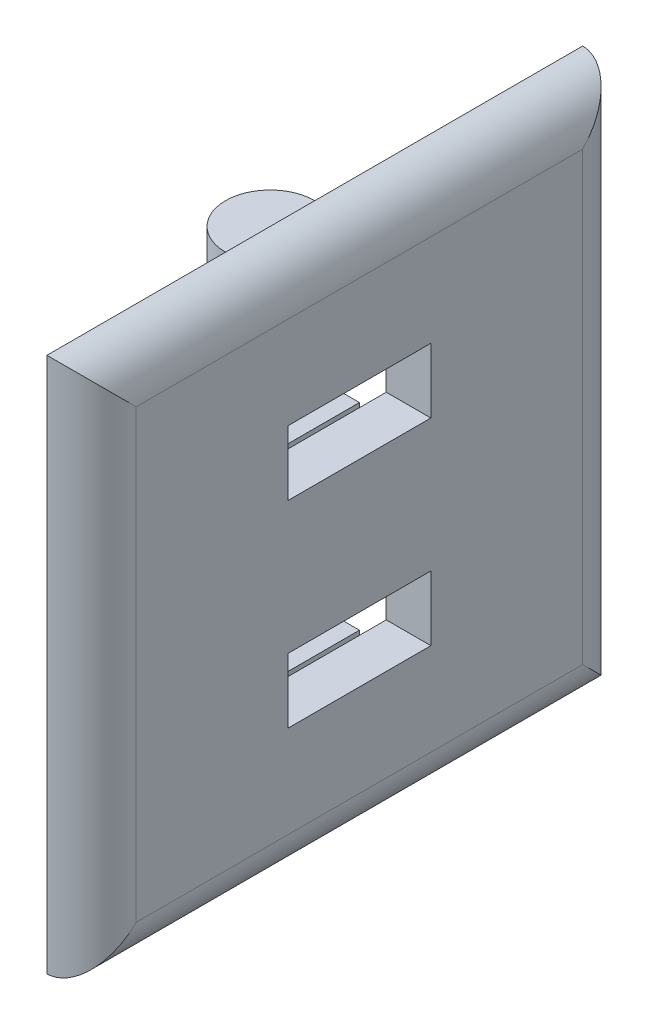
SolidWorks part; units mm, degrees
ref_plane "Front Plane" through (0, 0, 0) normal (1, 0, 0) x (0, 1, 0)
ref_plane "Top Plane" through (0, 0, 0) normal (0, 0, 1) x (0, 1, 0)
ref_plane "Right Plane" through (0, 0, 0) normal (0, 1, 0) x (-1, 0, 0)
sketch "Sketch2" plane through (0, 0, 0) normal (1, 0, 0) x (0, 1, 0)
  line L1 (-60, -60) -> (60, -60)
  line L2 (-60, -60) -> (-60, 60)
  line L3 (-60, 60) -> (60, 60)
  line L4 (60, -60) -> (60, 60)
  line L5 (-60, -60) -> (60, 60) construction
  line L6 (-60, 60) -> (60, -60) construction
  point P0 (0, 0)
  dimension "D1" = 120
  dimension "D2" = 120
extrude "Boss-Extrude1" add sketch "Sketch2" along normal mid plane 10
fillet "Fillet1" radius 10 4 edges at (5, 60, 0) (5, 0, -60) (5, -60, 0) (5, 0, 60)
sketch "Sketch4" plane through (0, 0, 0) normal (0, 1, 0) x (-1, 0, 0)
  line L0 (15, 10) -> (5, 10)
  line L1 (5, -60) -> (5, 60) construction
  line L2 (5, 10) -> (5, -10)
  line L3 (5, -10) -> (15, -10)
  arc A0 (15, -10) -> (15, 10) centre (15, 0) ccw
  dimension "D2" = 10
  dimension "D1" = 10
extrude "Boss-Extrude2" add sketch "Sketch4" along normal mid plane 100
sketch "Sketch3" plane through (5, 0, 0) normal (1, 0, 0) x (0, 1, 0)
  line L0 (-15.8333, 0) -> (15.8333, 0) construction
  line L2 (28.3333, 0) -> (60, 0) construction
  line L3 (60, -60) -> (60, 60) construction
  line L5 (-28.3333, 0) -> (-60, 0) construction
  line L6 (-28.3333, -15) -> (-15.8333, -15)
  line L7 (-28.3333, -15) -> (-28.3333, 15)
  line L8 (-28.3333, 15) -> (-15.8333, 15)
  line L9 (-15.8333, -15) -> (-15.8333, 15)
  line L10 (-28.3333, -15) -> (-15.8333, 15) construction
  line L11 (-28.3333, 15) -> (-15.8333, -15) construction
  line L12 (15.8333, -15) -> (28.3333, -15)
  line L13 (15.8333, -15) -> (15.8333, 15)
  line L14 (15.8333, 15) -> (28.3333, 15)
  line L15 (28.3333, -15) -> (28.3333, 15)
  line L16 (15.8333, -15) -> (28.3333, 15) construction
  line L17 (15.8333, 15) -> (28.3333, -15) construction
  line L18 (-60, 60) -> (-60, -60) construction
  point P19 (0, 0)
  point P20 (-22.0833, 0)
  point P22 (22.0833, 0)
  dimension "D1" = 12.5
  dimension "D2" = 30
  dimension "D3" = 30
  dimension "D4" = 12.5
extrude "Cut-Extrude1" cut sketch "Sketch3" against normal through all
sketch "Sketch5" plane through (5, 0, 0) normal (1, 0, 0) x (0, 1, 0)
  line L8 (14.8333, -16) -> (29.3333, -16)
  line L9 (29.3333, -16) -> (29.3333, 16)
  line L10 (29.3333, 16) -> (14.8333, 16)
  line L11 (14.8333, 16) -> (14.8333, -16)
  line L12 (14.8333, -16) -> (29.3333, -16)
  line L13 (29.3333, -16) -> (29.3333, 16)
  line L14 (29.3333, 16) -> (14.8333, 16)
  line L15 (14.8333, 16) -> (14.8333, -16)
  line L20 (-14.8333, 16) -> (-29.3333, 16)
  line L21 (-29.3333, 16) -> (-29.3333, -16)
  line L22 (-29.3333, -16) -> (-14.8333, -16)
  line L23 (-14.8333, -16) -> (-14.8333, 16)
  line L24 (-14.8333, 16) -> (-29.3333, 16)
  line L25 (-29.3333, 16) -> (-29.3333, -16)
  line L26 (-29.3333, -16) -> (-14.8333, -16)
  line L27 (-14.8333, -16) -> (-14.8333, 16)
  dimension "D1" = 1
  dimension "D2" = 1
extrude "Cut-Extrude2" cut sketch "Sketch5" against normal up to surface (10 mm away) up to face at (-5, 0, 0)
